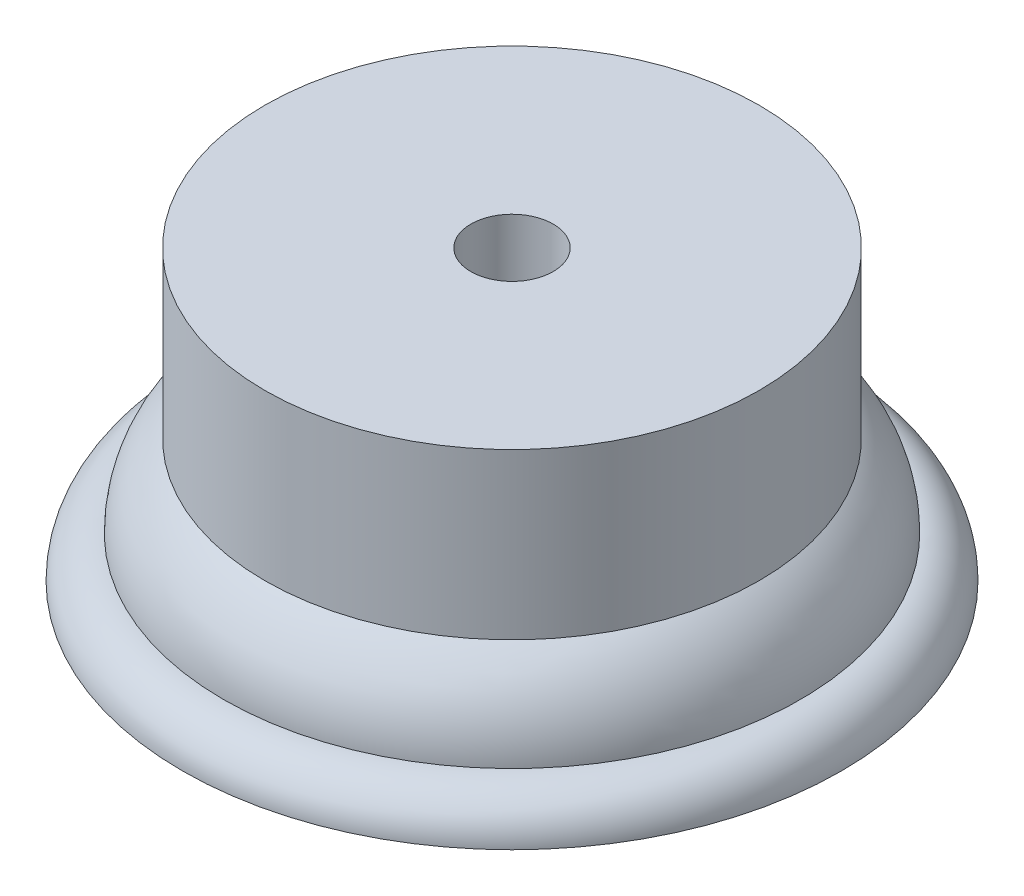
SolidWorks part; units mm, degrees
ref_plane "Front Plane" through (0, 0, 0) normal (0, 0, 1) x (1, 0, 0)
ref_plane "Top Plane" through (0, 0, 0) normal (0, 1, 0) x (1, 0, 0)
ref_plane "Right Plane" through (0, 0, 0) normal (1, 0, 0) x (0, 0, -1)
sketch "Sketch1" plane through (0, 0, 0) normal (0, 1, 0) x (1, 0, 0)
  circle A0 centre (0, 0) radius 8
  dimension "D1" = 16
extrude "Blade Holder Extrude" add sketch "Sketch1" along normal blind 1
sketch "Sketch2" plane through (0, 1, 0) normal (0, 1, 0) x (1, 0, 0)
  circle A0 centre (0, 0) radius 7
  dimension "D1" = 14
extrude "Blade Holder Extrude 2" add sketch "Sketch2" along normal blind 2
sketch "Sketch3" plane through (0, 3, 0) normal (0, 1, 0) x (1, 0, 0)
  circle A0 centre (0, 0) radius 6
  dimension "D1" = 12
extrude "Blade Holder Extrude 3" add sketch "Sketch3" along normal blind 4
sketch "Sketch4" plane through (0, 7, 0) normal (0, 1, 0) x (1, 0, 0)
  circle A0 centre (0, 0) radius 1
  dimension "D1" = 2
extrude "Hole for Screw (Blade Holder)" cut sketch "Sketch4" against normal blind 24
fillet "Blade Holder Fillet 1" radius 1 1 edges at (0, 1, 8)
fillet "Blade Holder Fillet 2" radius 2.5 1 edges at (0, 3, 7)
